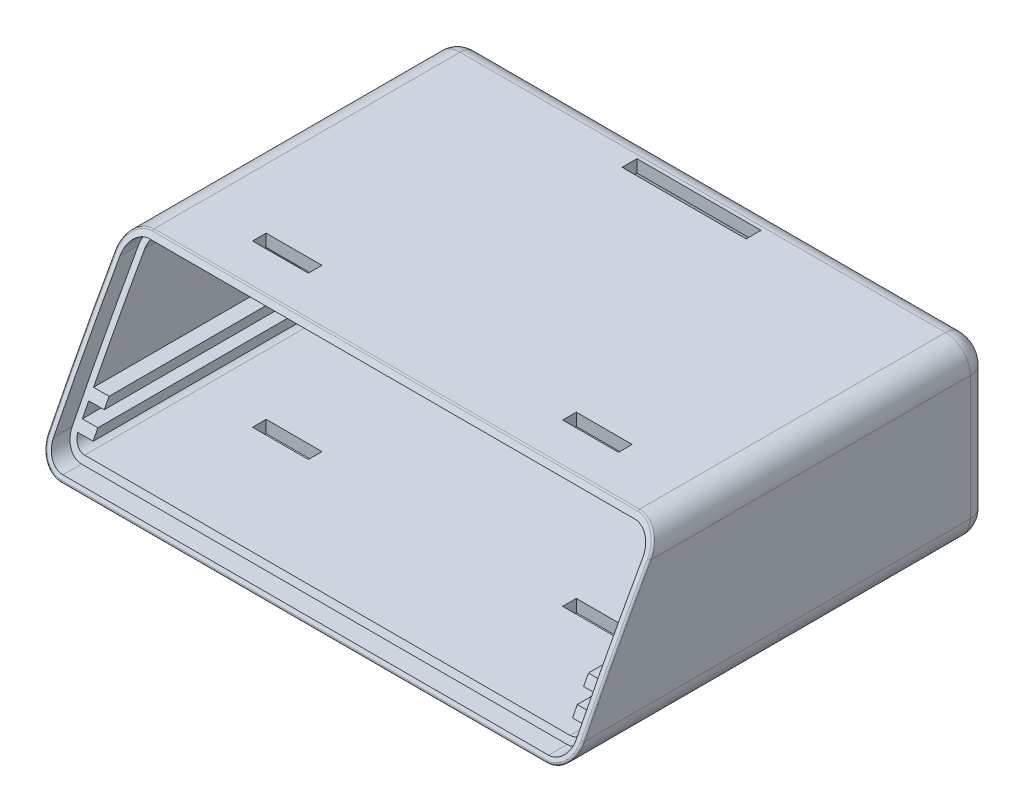
SolidWorks part; units mm, degrees
ref_plane "Front Plane" through (0, 0, 0) normal (0, 0, 1) x (1, 0, 0)
ref_plane "Top Plane" through (0, 0, 0) normal (0, 1, 0) x (1, 0, 0)
ref_plane "Right Plane" through (0, 0, 0) normal (1, 0, 0) x (0, 0, -1)
sketch "Sketch1" plane through (0, 0, 0) normal (0, 1, 0) x (1, 0, 0)
  line L1 (-43.14, -33.75) -> (43.14, -33.75)
  line L2 (-43.14, -33.75) -> (-43.14, 33.75)
  line L3 (-43.14, 33.75) -> (43.14, 33.75)
  line L4 (43.14, -33.75) -> (43.14, 33.75)
  line L5 (-43.14, -33.75) -> (43.14, 33.75) construction
  line L6 (-43.14, 33.75) -> (43.14, -33.75) construction
  point P0 (0, 0)
  dimension "D1" = 67.5
  dimension "D2" = 86.28
extrude "Boss-Extrude1" add sketch "Sketch1" along normal blind 28
fillet "Fillet1" radius 4 4 edges at (43.14, 28, 0) (43.14, 0, 0) (-43.14, 0, 0) (-43.14, 28, 0)
shell "Shell1" thickness 2
sketch "Sketch2" plane through (-43.14, 0, 0) normal (-1, 0, 0) x (0, 0, 1)
  line L0 (-33.75, 28) -> (33.75, 28) construction
  line L1 (18.75, 28) -> (33.75, 28)
  line L2 (33.75, 28) -> (33.75, 0)
  arc A0 (33.75, 0) -> (18.75, 28) centre (-392.2189, -210.1797) ccw
  dimension "D1" = 15
  dimension "D2" = 475
extrude "Cut-Extrude1" cut sketch "Sketch2" against normal through all
sketch "Sketch3" plane through (0, 0, -33.75) normal (0, 0, -1) x (-1, 0, 0)
  line L0 (-7.15, 18.7) -> (7.15, 18.7)
  line L1 (-6.95, 18.5) -> (6.95, 18.5) construction
  line L2 (-6.95, 18.5) -> (-6.95, 2.2) construction
  line L3 (-6.95, 2.2) -> (6.95, 2.2) construction
  line L4 (6.95, 18.5) -> (6.95, 2.2) construction
  line L5 (7.15, 18.7) -> (7.15, 2)
  line L6 (-7.15, 2) -> (7.15, 2)
  line L7 (-7.15, 18.7) -> (-7.15, 2)
  line L8 (27.25, 17.2) -> (38.3, 17.2)
  line L9 (27.45, 17) -> (38.1, 17) construction
  line L10 (27.45, 17) -> (27.45, 3.35) construction
  line L11 (27.45, 3.35) -> (38.1, 3.35) construction
  line L12 (38.1, 17) -> (38.1, 3.35) construction
  line L13 (38.3, 17.2) -> (38.3, 3.15)
  line L14 (27.25, 3.15) -> (38.3, 3.15)
  line L15 (27.25, 17.2) -> (27.25, 3.15)
  dimension "D1" = 0.2
  dimension "D2" = 0.2
extrude "Cut-Extrude2" cut sketch "Sketch3" against normal up to surface (2 mm away) up to face at (0, 14, -31.75)
fillet "Fillet2" radius 3 8 edges at (41.9684, 26.8284, -33.75) (43.14, 14, -33.75) (41.9684, 1.1716, -33.75) (0, 0, -33.75) (-41.9684, 1.1716, -33.75) (-43.14, 14, -33.75) (-41.9684, 26.8284, -33.75) (0, 28, -33.75)
sketch "Sketch4" plane through (0, 0, -31.75) normal (0, 0, 1) x (1, 0, 0)
  line L0 (-7.15, 2) -> (7.15, 2)
  line L1 (-7.15, 1) -> (7.15, 1)
  line L2 (7.15, 1) -> (39.14, 1)
  line L3 (42.14, 4) -> (42.14, 24)
  line L4 (39.14, 27) -> (-39.14, 27)
  line L5 (-42.14, 24) -> (-42.14, 4)
  line L6 (-39.14, 1) -> (-7.15, 1)
  line L8 (-7.15, 18.7) -> (7.15, 18.7)
  line L9 (7.15, 18.7) -> (7.15, 2)
  line L10 (7.15, 2) -> (39.14, 2)
  line L11 (41.14, 4) -> (41.14, 24)
  line L12 (39.14, 26) -> (-39.14, 26)
  line L13 (-41.14, 24) -> (-41.14, 4)
  line L14 (-39.14, 2) -> (-7.15, 2)
  line L15 (-7.15, 2) -> (-7.15, 18.7)
  line L18 (7.15, 2) -> (39.14, 2)
  line L19 (41.14, 4) -> (41.14, 24)
  line L20 (39.14, 26) -> (-39.14, 26)
  line L21 (-41.14, 24) -> (-41.14, 4)
  line L22 (-39.14, 2) -> (-7.15, 2)
  arc A0 (39.14, 1) -> (42.14, 4) centre (39.14, 4) ccw
  arc A1 (42.14, 24) -> (39.14, 27) centre (39.14, 24) ccw
  arc A2 (-39.14, 27) -> (-42.14, 24) centre (-39.14, 24) ccw
  arc A3 (-42.14, 4) -> (-39.14, 1) centre (-39.14, 4) ccw
  arc A4 (39.14, 2) -> (41.14, 4) centre (39.14, 4) ccw
  arc A5 (41.14, 24) -> (39.14, 26) centre (39.14, 24) ccw
  arc A6 (-39.14, 26) -> (-41.14, 24) centre (-39.14, 24) ccw
  arc A7 (-41.14, 4) -> (-39.14, 2) centre (-39.14, 4) ccw
  arc A8 (39.14, 2) -> (41.14, 4) centre (39.14, 4) ccw
  arc A9 (41.14, 24) -> (39.14, 26) centre (39.14, 24) ccw
  arc A10 (-39.14, 26) -> (-41.14, 24) centre (-39.14, 24) ccw
  arc A11 (-41.14, 4) -> (-39.14, 2) centre (-39.14, 4) ccw
  dimension "D1" = 0
  dimension "D2" = 1
extrude "Cut-Extrude3" cut sketch "Sketch4" against normal offset from surface (19.4971 mm away) 3 from offset 80
fillet "Fillet3" radius 0.3 8 edges at (41.7842, 27.0013, 19.3272) (43.14, 14.064, 26.517) (41.4452, 0.7311, 33.3885) (0, 0, 33.75) (-42.0581, 1.2642, 33.1239) (-43.14, 14.064, 26.517) (-41.3892, 27.3077, 19.1504) (0, 28, 18.75)
sketch "Sketch5" plane through (0, 0, -31.75) normal (0, 0, 1) x (1, 0, 0)
  line L0 (41.14, 24) -> (41.14, 4) construction
  line L1 (41.14, 5.25) -> (38.64, 5.25)
  line L2 (41.14, 5.25) -> (41.14, 3.75)
  line L3 (41.14, 3.75) -> (38.64, 3.75)
  line L4 (38.64, 5.25) -> (38.64, 3.75)
  line L5 (34.8894, 7.05) -> (40.64, 7.05) construction
  line L6 (41.14, 7.25) -> (38.64, 7.25)
  line L7 (41.14, 7.25) -> (41.14, 8.75)
  line L8 (41.14, 8.75) -> (38.64, 8.75)
  line L9 (38.64, 7.25) -> (38.64, 8.75)
  line L10 (-40.64, 7.05) -> (40.64, 7.05) construction
  line L11 (40.64, 5.45) -> (34.7752, 5.45) construction
  line L12 (-40.64, 5.45) -> (40.64, 5.45) construction
  line L13 (-41.14, 4) -> (-41.14, 24) construction
  line L14 (-41.14, 8.75) -> (-38.64, 8.75)
  line L15 (-41.14, 8.75) -> (-41.14, 7.25)
  line L16 (-41.14, 7.25) -> (-38.64, 7.25)
  line L17 (-38.64, 8.75) -> (-38.64, 7.25)
  line L19 (-41.14, 5.25) -> (-38.64, 5.25)
  line L20 (-41.14, 5.25) -> (-41.14, 3.75)
  line L21 (-41.14, 3.75) -> (-38.64, 3.75)
  line L22 (-38.64, 5.25) -> (-38.64, 3.75)
  dimension "D1" = 0.2
  dimension "D2" = 0.2
  dimension "D3" = 1.5
  dimension "D4" = 2.5
extrude "Boss-Extrude2" add sketch "Sketch5" along normal up to surface (59.8691 mm away)
sketch "Sketch6" plane through (0, 28, 0) normal (0, 1, 0) x (1, 0, 0)
  line L0 (0, 0) -> (0, 30.75) construction
  line L1 (21.5, -10.33) -> (28.5, -10.33) construction
  line L2 (21.5, -10.33) -> (21.5, -12.13) construction
  line L3 (21.5, -12.13) -> (28.5, -12.13) construction
  line L4 (28.5, -10.33) -> (28.5, -12.13) construction
  line L5 (20.5, -10.13) -> (29.5, -10.13)
  line L6 (20.5, -10.13) -> (20.5, -12.33)
  line L7 (20.5, -12.33) -> (29.5, -12.33)
  line L8 (29.5, -10.13) -> (29.5, -12.33)
  line L9 (39.14, 30.75) -> (-39.14, 30.75) construction
  line L10 (-28.5, -10.33) -> (-28.5, -12.13) construction
  line L11 (-21.5, -12.13) -> (-28.5, -12.13) construction
  line L12 (-21.5, -10.33) -> (-21.5, -12.13) construction
  line L13 (-21.5, -10.33) -> (-28.5, -10.33) construction
  line L14 (-29.5, -10.13) -> (-29.5, -12.33)
  line L15 (-20.5, -12.33) -> (-29.5, -12.33)
  line L16 (-20.5, -10.13) -> (-20.5, -12.33)
  line L17 (-20.5, -10.13) -> (-29.5, -10.13)
  dimension "D1" = 0.2
  dimension "D2" = 0.2
  dimension "D3" = 1
  dimension "D4" = 1
extrude "Cut-Extrude4" cut sketch "Sketch6" against normal through all
sketch "Sketch7" plane through (0, 28, 0) normal (0, 1, 0) x (1, 0, 0)
  line L0 (-39.14, 33.75) -> (39.14, 33.75) construction
  line L1 (-10, 30.15) -> (10, 30.15)
  line L2 (-10, 30.15) -> (-10, 27.75)
  line L3 (-10, 27.75) -> (10, 27.75)
  line L4 (10, 30.15) -> (10, 27.75)
  line L5 (0, 27.75) -> (0, 0) construction
  dimension "D1" = 3.6
  dimension "D2" = 2.4
  dimension "D3" = 20
extrude "Cut-Extrude5" cut sketch "Sketch7" against normal up to surface (2 mm away) up to face at (-25, 26, 11.23)
